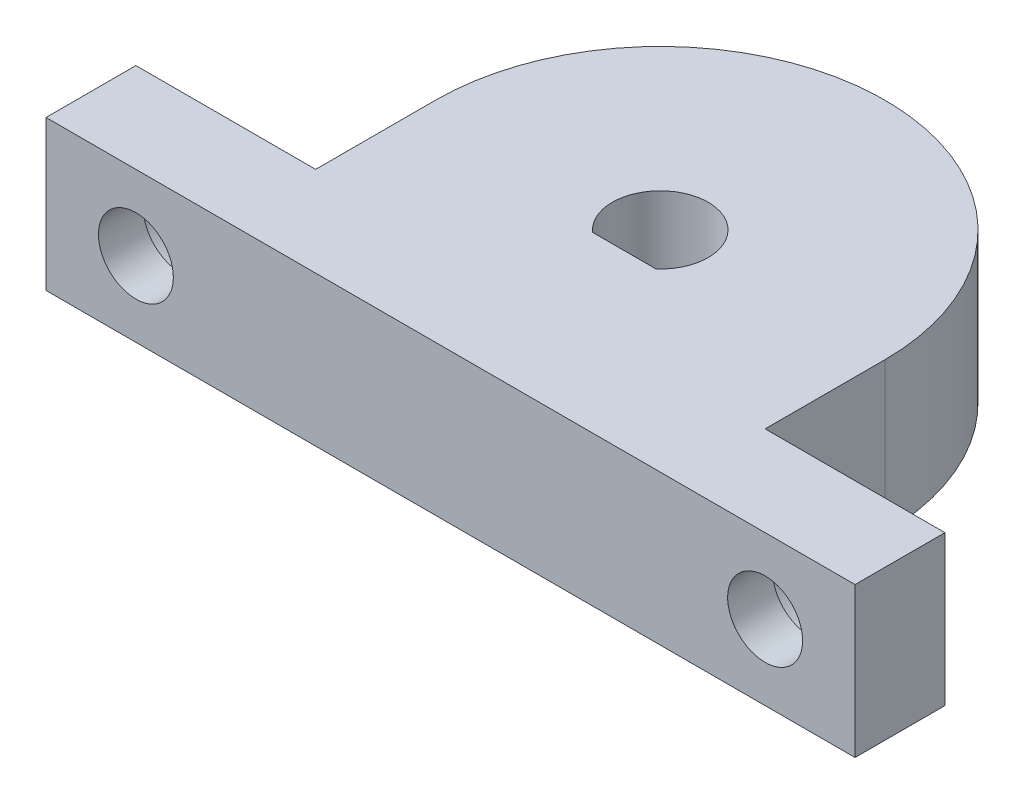
SolidWorks part; units mm, degrees
ref_plane "前视基准面" through (0, 0, 0) normal (0, 0, 1) x (1, 0, 0)
ref_plane "上视基准面" through (0, 0, 0) normal (0, 1, 0) x (1, 0, 0)
ref_plane "右视基准面" through (0, 0, 0) normal (1, 0, 0) x (0, 0, -1)
other "Configuration Table"
sketch "草图2" plane through (0, 0, 0) normal (0, 1, 0) x (1, 0, 0)
  line L9 (0, 0) -> (170, 0)
  line L10 (0, 0) -> (0, -20)
  line L11 (0, -20) -> (170, -20)
  line L12 (170, 0) -> (170, -20)
  dimension "D1" = 170
  dimension "D2" = 20
extrude "凸台-拉伸1" add sketch "草图2" along normal blind 23
sketch "草图3" plane through (0, 23, 0) normal (0, 1, 0) x (1, 0, 0)
  line L0 (123.9417, -11.2) -> (126.0583, -11.2)
  line L1 (158.9417, -11.2) -> (161.0583, -11.2)
  line L2 (0, -20) -> (170, -20) construction
  line L3 (170, -20) -> (170, 0) construction
  circle A0 centre (125, -10) radius 1.6
  circle A1 centre (160, -10) radius 1.6
  dimension "D1" = 3.2
  dimension "D2" = 10
  dimension "D3" = 45
  dimension "D4" = 10
  dimension "D5" = 10
  dimension "D6" = 1.2
extrude "切除-拉伸1" cut sketch "草图3" against normal through all contours L1 A1 | L0 A0 region at (125, 23, 9.8941) region at (160, 23, 9.8941)
sketch "草图4" plane through (170, 0, 0) normal (1, 0, 0) x (0, 0, -1)
  line L0 (0, 23) -> (0, 0) construction
  line L1 (0, 18) -> (-17, 18)
  line L2 (0, 18) -> (0, 5)
  line L3 (0, 5) -> (-17, 5)
  line L4 (-17, 18) -> (-17, 5)
  line L5 (-17, 18) -> (-17, 23)
  line L6 (-20, 23) -> (0, 23) construction
  line L7 (-17, 5) -> (-17, 0)
  line L8 (-20, 0) -> (0, 0) construction
  line L9 (-20, 23) -> (-20, 0) construction
  line M6 (0, 0) -> (0, 23)
  dimension "D1" = 13
  dimension "D2" = 3
extrude "切除-拉伸2" cut sketch "草图4" against normal blind 30 contours L1 L4 L3 M6 region at (170, 11.5, 8.5)
sketch "草图5" plane through (0, 23, 0) normal (0, 1, 0) x (1, 0, 0)
  line L0 (117.5, -10) -> (117.5, -20)
  line L1 (0, -20) -> (170, -20) construction
  line L2 (132.5, -10) -> (132.5, -20)
  line L3 (152.5, -10) -> (152.5, -20)
  line L4 (167.5, -10) -> (167.5, -20)
  line L5 (132.5, -17) -> (152.5, -17)
  line L6 (167.5, -17) -> (170, -17)
  line L7 (170, -20) -> (170, 0) construction
  line L8 (132.5, -17) -> (102.5, -17)
  line L9 (102.5, -17) -> (102.5, 0)
  line L10 (170, 0) -> (0, 0) construction
  line L11 (102.5, -17) -> (102.5, -20)
  circle A0 centre (125, -10) radius 7.5
  circle A1 centre (160, -10) radius 7.5
  arc A2 (126.0583, -11.2) -> (123.9417, -11.2) centre (125, -10) ccw construction
  arc A3 (161.0583, -11.2) -> (158.9417, -11.2) centre (160, -10) ccw construction
  line M10 (0, 0) -> (0, -20)
  line M11 (0, -20) -> (170, -20)
  line M12 (170, -20) -> (170, 0)
  line M13 (170, 0) -> (0, 0)
  dimension "D1" = 15
  dimension "D2" = 3
  dimension "D3" = 30
extrude "切除-拉伸3" cut sketch "草图5" against normal through all contours L8 L9 L0 M13 M10 M11 | A1 L4 L6 L9 L8 L0 A0 L2 L5 L3 M12 M13 region at (133.0731, 23, 7.5108) region at (51.25, 23, 10)
sketch "草图6" plane through (0, 23, 0) normal (0, 1, 0) x (1, 0, 0)
  line L0 (132.5, -10) -> (132.5, -17) construction
  line L1 (102.5, -17) -> (170, -17)
  line L2 (102.5, -17) -> (102.5, -20)
  line L3 (102.5, -20) -> (170, -20)
  line L4 (170, -17) -> (170, -20)
  line L5 (152.5, -17) -> (170, -17)
  line L9 (117.5, -17) -> (132.5, -17)
  line L10 (117.5, -17) -> (117.5, -2.5)
  line L11 (117.5, -2.5) -> (132.5, -2.5)
  line L12 (132.5, -17) -> (132.5, -2.5)
  arc A1 (132.5, -10) -> (117.5, -10) centre (125, -10) ccw construction
extrude "切除-拉伸4" cut sketch "草图6" against normal through all contours L1 L2 L3 L4 | L10 L11 L12 L9
sketch "草图7" plane through (152.5, 0, 0) normal (-1, 0, 0) x (0, 0, 1)
  line L1 (-2.4504, 24.4851) -> (22.898, 24.4851)
  line L2 (-2.4504, 24.4851) -> (-2.4504, 14.9695)
  line L3 (-2.4504, 14.9695) -> (22.898, 14.9695)
  line L4 (22.898, 24.4851) -> (22.898, 14.9695)
  point P4 (22.898, 14.9695)
extrude "切除-拉伸5" cut sketch "草图7" against normal through all
sketch "草图8" plane through (0, 0, 17) normal (0, 0, 1) x (1, 0, 0)
  line L0 (152.5, 0) -> (167.5, 0) construction
  line L1 (146.5, 5) -> (173.5, 5)
  line L2 (146.5, 5) -> (146.5, 0)
  line L3 (146.5, 0) -> (173.5, 0)
  line L4 (173.5, 5) -> (173.5, 0)
  line L5 (152.5, 5) -> (167.5, 5) construction
  line L6 (152.5, 0) -> (152.5, 5) construction
  line L7 (167.5, 0) -> (167.5, 5) construction
  line L8 (152.5, 5) -> (146.5, 0) construction
  line L9 (167.5, 5) -> (173.5, 0) construction
  circle A0 centre (149.5, 2.5) radius 1.25
  circle A1 centre (170.5, 2.5) radius 2
  circle A2 centre (170.5, 2.5) radius 1.25
  circle A3 centre (149.5, 2.5) radius 2
  point P19 (0, 0)
  dimension "D3" = 4
  dimension "D4" = 2.5
  dimension "D1" = 6
  dimension "D2" = 6
extrude "凸台-拉伸2" add sketch "草图8" against normal blind 3 contours L3 L4 L1 L2 | A2 | A0
extrude "切除-拉伸6" cut sketch "草图8<3>" along normal blind 1.5 from surface contours A1 | A3 starting at face at (171.75, 2.5, 14)
sketch "草图8<3>" plane through (0, 0, 17) normal (0, 0, 1) x (1, 0, 0) same geometry as "草图8"
